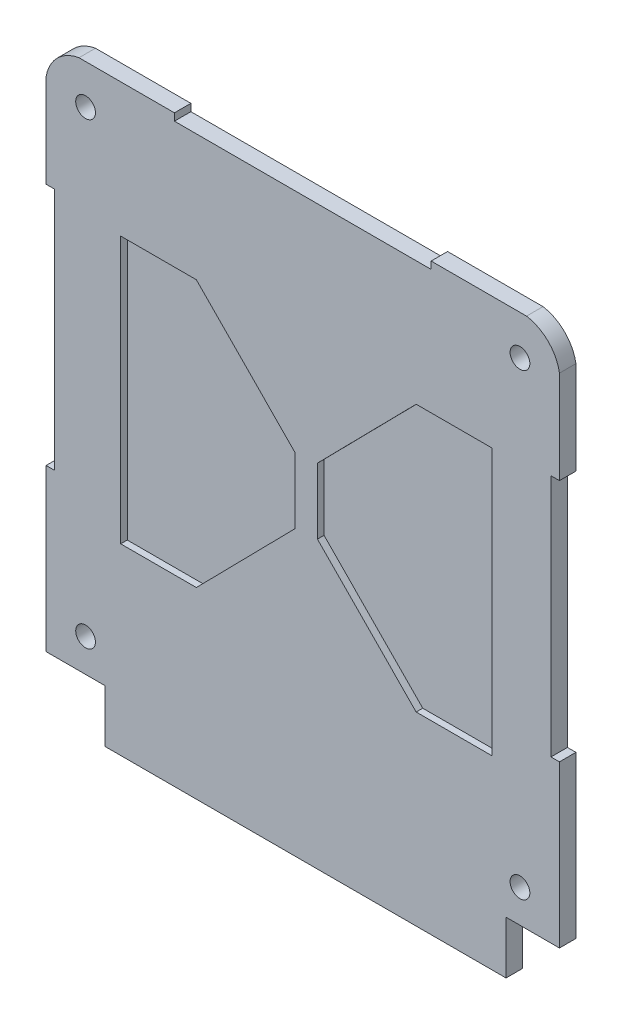
SolidWorks part; units mm, degrees
ref_plane "Front Plane" through (0, 0, 0) normal (0, 0, 1) x (1, 0, 0)
ref_plane "Top Plane" through (0, 0, 0) normal (0, 1, 0) x (1, 0, 0)
ref_plane "Right Plane" through (0, 0, 0) normal (1, 0, 0) x (0, 0, -1)
sketch "Sketch1" plane through (0, 0, 0) normal (0, 0, 1) x (1, 0, 0)
  line L0 (-75.42, 42.35) -> (-75.42, -31.65)
  line L1 (-75.42, -31.65) -> (-78, -31.65)
  line L2 (-78, -31.65) -> (-78, -80.65)
  line L3 (-78, -80.65) -> (78, -80.65)
  line L4 (78, -80.65) -> (78, -31.65)
  line L5 (78, -31.65) -> (75.4199, -31.65)
  line L6 (75.4199, -31.65) -> (75.4199, 42.35)
  line L7 (75.4199, 42.35) -> (78, 42.35)
  line L8 (78, 42.35) -> (78, 70.65)
  line L9 (68, 80.65) -> (39, 80.65)
  line L10 (39, 80.65) -> (39, 78.45)
  line L11 (39, 78.45) -> (-39, 78.45)
  line L12 (-39, 78.45) -> (-39, 80.65)
  line L13 (-39, 80.65) -> (-68, 80.65)
  line L14 (-78, 70.65) -> (-78, 42.35)
  line L15 (-78, 42.35) -> (-75.42, 42.35)
  arc A0 (78, 70.65) -> (68, 80.65) centre (65.9999, 68.6499) ccw
  arc A1 (-68, 80.65) -> (-78, 70.65) centre (-66.0001, 68.6501) ccw
extrude "Boss-Extrude1" add sketch "Sketch1" along normal blind 5
sketch "Sketch2" plane through (0, 0, 5) normal (0, 0, 1) x (1, 0, 0)
  line L0 (-55.3353, 40.0558) -> (-55.3353, -40.9442)
  line L1 (-55.3353, -40.9442) -> (-32.3353, -40.9442)
  line L2 (-32.3353, -40.9442) -> (-2.3353, -10.4442)
  line L3 (-2.3353, -10.4442) -> (-2.3353, 9.5559)
  line L4 (-2.3353, 9.5559) -> (-32.3353, 40.0558)
  line L5 (-32.3353, 40.0558) -> (-55.3353, 40.0558)
  line L6 (4.4582, 10.1927) -> (4.4582, -9.8073)
  line L7 (4.4582, -9.8073) -> (34.4582, -40.3073)
  line L8 (34.4582, -40.3073) -> (57.4582, -40.3073)
  line L9 (57.4582, -40.3073) -> (57.4582, 40.6927)
  line L10 (57.4582, 40.6927) -> (34.4582, 40.6927)
  line L11 (34.4582, 40.6927) -> (4.4582, 10.1927)
extrude "Cut-Extrude1" cut sketch "Sketch2" against normal blind 2
sketch "Sketch3" plane through (0, 0, 5) normal (0, 0, 1) x (1, 0, 0)
  line L0 (-74.6023, 77.2523) -> (-66.0001, 68.6501) construction
  line L1 (74.6023, 77.2523) -> (65.9999, 68.6499) construction
  line L2 (-66.0001, -80.65) -> (-66.0001, -70.65) construction
  line L3 (-78, -80.65) -> (78, -80.65) construction
  line L4 (65.9999, -80.65) -> (65.9999, -70.65) construction
  arc A0 (-68, 80.65) -> (-78, 70.65) centre (-66.0001, 68.6501) ccw construction
  circle A1 centre (-66.0001, 68.6501) radius 3
  arc A2 (78, 70.65) -> (68, 80.65) centre (65.9999, 68.6499) ccw construction
  circle A3 centre (65.9999, 68.6499) radius 3
  circle A4 centre (-66.0001, -70.65) radius 3
  circle A5 centre (65.9999, -70.65) radius 3
  point P22 (0, 0)
  point P23 (0, 0)
extrude "Cut-Extrude2" cut sketch "Sketch3" against normal blind 42
sketch "Sketch6" plane through (0, 0, 0) normal (0, 0, -1) x (-1, 0, 0)
  line L0 (-59.9951, -61.6656) -> (61.5049, -61.6656) construction
  line L1 (-63.9951, -59.6656) -> (-59.9951, -59.6656)
  line L2 (-63.9951, -59.6656) -> (-63.9951, -63.6656)
  line L3 (-63.9951, -63.6656) -> (-59.9951, -63.6656)
  line L4 (-59.9951, -59.6656) -> (-59.9951, -63.6656)
  line L5 (-63.9951, -59.6656) -> (-59.9951, -63.6656) construction
  line L6 (-63.9951, -63.6656) -> (-59.9951, -59.6656) construction
  line L7 (61.5049, -59.6656) -> (65.5049, -59.6656)
  line L8 (61.5049, -59.6656) -> (61.5049, -63.6656)
  line L9 (61.5049, -63.6656) -> (65.5049, -63.6656)
  line L10 (65.5049, -59.6656) -> (65.5049, -63.6656)
  line L11 (61.5049, -59.6656) -> (65.5049, -63.6656) construction
  line L12 (61.5049, -63.6656) -> (65.5049, -59.6656) construction
  point P4 (-61.9951, -61.6656)
  point P9 (63.5049, -61.6656)
extrude "Cut-Extrude4" cut sketch "Sketch6" against normal blind 3
sketch "Sketch7" plane through (0, 0, 0) normal (0, 0, -1) x (-1, 0, 0)
  line L0 (-63.9951, -59.6656) -> (-63.9951, 47.6605)
  line L1 (65.5049, -59.6656) -> (65.5049, 47.6605)
  line L2 (65.5049, 47.6605) -> (-63.9951, 47.6605)
  line L3 (-59.9951, -59.6656) -> (-59.9951, 44.4761)
  line L4 (61.5049, -59.6656) -> (61.5049, 44.4761)
  line L5 (61.5049, 44.4761) -> (-59.9951, 44.4761)
  line L6 (-63.9951, -59.6656) -> (-59.9951, -59.6656)
  line L7 (61.5049, -59.6656) -> (65.5049, -59.6656)
extrude "Cut-Extrude5" cut sketch "Sketch7" against normal blind 3
sketch "Sketch8" plane through (0, 0, 0) normal (0, 0, -1) x (-1, 0, 0)
  line L0 (-61.77, -80.65) -> (60.13, -80.65)
  line L1 (78, -80.65) -> (-78, -80.65) construction
  line L3 (-61.77, -80.65) -> (60.13, -80.65)
  line L4 (-61.77, -80.65) -> (-61.77, -96.65)
  line L5 (-61.77, -96.65) -> (60.13, -96.65)
  line L6 (60.13, -80.65) -> (60.13, -96.65)
  line L7 (-61.77, -80.65) -> (60.13, -96.65) construction
  line L8 (-61.77, -96.65) -> (60.13, -80.65) construction
  point P5 (-0.82, -80.65)
  point P7 (-0.82, -88.65)
  line M28 (-78, -80.65) -> (78, -80.65)
  dimension "D1" = 16
extrude "Boss-Extrude2" add sketch "Sketch8" against normal blind 5 contours L6 L4 L5 M28 region at (0.82, -88.65, 0)
